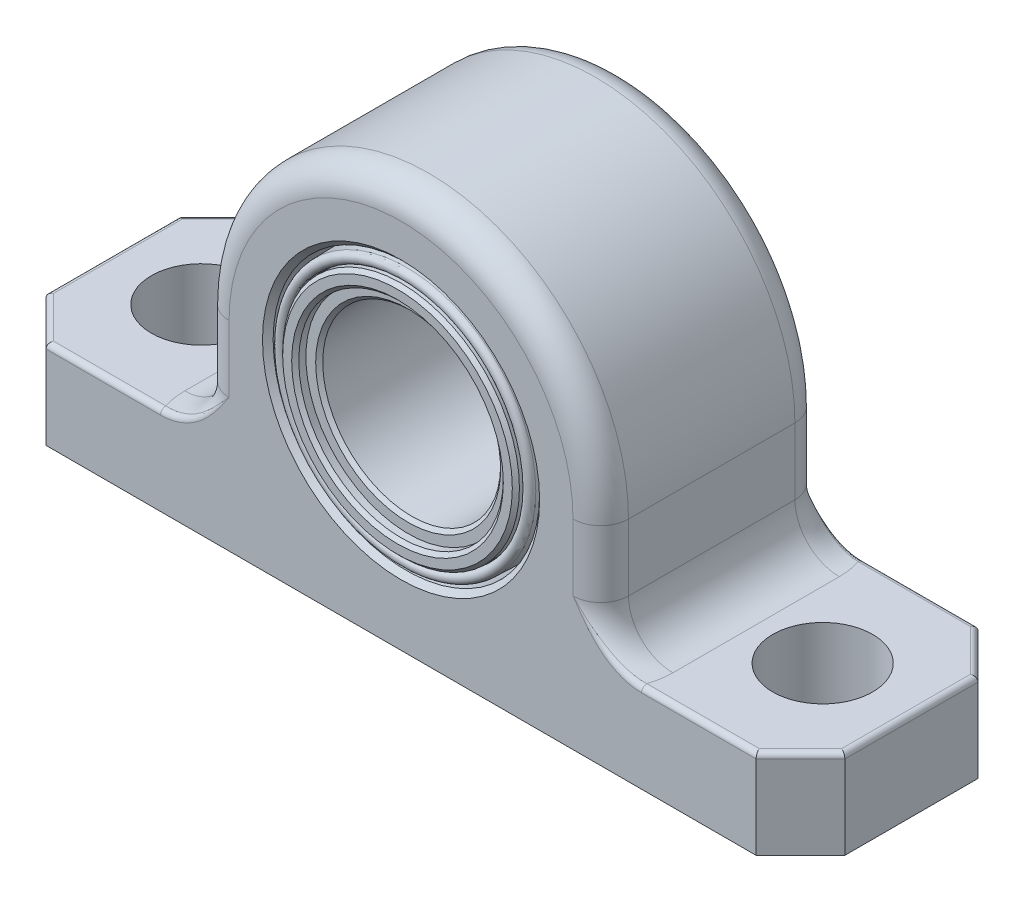
SolidWorks part; units mm, degrees
ref_plane "Front Plane" through (0, 0, 0) normal (0, 0, 1) x (1, 0, 0)
ref_plane "Top Plane" through (0, 0, 0) normal (0, 1, 0) x (1, 0, 0)
ref_plane "Right Plane" through (0, 0, 0) normal (1, 0, 0) x (0, 0, -1)
sketch "Sketch1" plane through (0, 0, 0) normal (0, 0, 1) x (1, 0, 0)
  line L0 (-28.575, 0) -> (28.575, 0)
  line L1 (28.575, 0) -> (28.575, 6.35)
  line L2 (-28.575, 0) -> (-28.575, 6.35)
  line L3 (-28.575, 6.35) -> (-14.2875, 6.35)
  line L4 (28.575, 6.35) -> (14.2875, 6.35)
  line L5 (-14.2875, 6.35) -> (-14.2875, 14.2875)
  line L6 (14.2875, 6.35) -> (14.2875, 14.2875)
  line L7 (0, 0) -> (0, 28.575) construction
  line L8 (4.4991, 18.7866) -> (10.1028, 24.3903) construction
  circle A0 centre (0, 14.2875) radius 6.3627
  arc A1 (14.2875, 14.2875) -> (-14.2875, 14.2875) centre (0, 14.2875) ccw
  circle A2 centre (0, 14.2875) radius 9.5326 construction
  point P16 (6.7406, 21.0281)
  point P17 (0, 20.6502)
  point P18 (0, 23.8201)
  dimension "D1" = 45
  dimension "ID" = 12.7254
  dimension "Overall Height" = 28.575
  dimension "Overall Length" = 57.15
  dimension "CAD B" = 6.35
  dimension "Center Height" = 14.2875
  dimension "D2" = 7.9248
  dimension "D3" = 3.1699
sketch "Sketch2" plane through (0, 0, 0) normal (0, 1, 0) x (1, 0, 0)
  line L0 (-22.225, 0) -> (22.225, 0) construction
  line L1 (-28.575, -7.9375) -> (28.575, 7.9375) construction
  line L2 (-28.575, 7.9375) -> (28.575, 7.9375)
  line L3 (-28.575, 7.9375) -> (-28.575, -7.9375)
  line L4 (-28.575, -7.9375) -> (28.575, -7.9375)
  line L5 (28.575, 7.9375) -> (28.575, -7.9375)
  circle A0 centre (-22.225, 0) radius 3.5719
  circle A1 centre (22.225, 0) radius 3.5719
  dimension "Mounting Hole" = 7.1437
  dimension "Mounting Center" = 44.45
  dimension "Overall Width" = 15.875
sketch "Sketch3" plane through (0, 0, 0) normal (0, 0, 1) x (1, 0, 0)
  line L0 (-28.575, 0) -> (-28.575, 6.35) construction
  line L1 (-28.575, 0) -> (28.575, 0) construction
  line L2 (-28.575, 6.35) -> (-14.2875, 6.35) construction
  line L3 (28.575, 6.35) -> (14.2875, 6.35) construction
  line L4 (28.575, 0) -> (28.575, 6.35) construction
  line L5 (14.2875, 6.35) -> (14.2875, 14.2875) construction
  line L6 (-14.2875, 6.35) -> (-14.2875, 14.2875) construction
  line L7 (-28.575, 0) -> (-28.575, 6.35)
  line L8 (-28.575, 0) -> (28.575, 0)
  line L9 (-28.575, 6.35) -> (-14.2875, 6.35)
  line L10 (28.575, 6.35) -> (14.2875, 6.35)
  line L11 (28.575, 0) -> (28.575, 6.35)
  line L12 (14.2875, 6.35) -> (14.2875, 14.2875)
  line L13 (-14.2875, 6.35) -> (-14.2875, 14.2875)
  arc A0 (14.2875, 14.2875) -> (-14.2875, 14.2875) centre (0, 14.2875) ccw construction
  circle A1 centre (0, 14.2875) radius 9.5326 construction
  arc A2 (14.2875, 14.2875) -> (-14.2875, 14.2875) centre (0, 14.2875) ccw
  circle A3 centre (0, 14.2875) radius 9.5326
extrude "Boss-Extrude1" add sketch "Sketch3" against normal up to vertex (7.9375 mm away) and the other way up to vertex (7.9375 mm away) up to point (-28.575, 0, -7.9375) other way up to point (-28.575, 0, 7.9375)
sketch "Sketch4" plane through (0, 0, 0) normal (0, 1, 0) x (1, 0, 0)
  circle A0 centre (-22.225, 0) radius 3.5719 construction
  circle A1 centre (22.225, 0) radius 3.5719 construction
  circle A2 centre (-22.225, 0) radius 3.5719
  circle A3 centre (22.225, 0) radius 3.5719
extrude "Cut-Extrude1" cut sketch "Sketch4" along normal through all
chamfer "Chamfer1" distance 3.175 angle 45 4 edges at (-28.575, 3.175, -7.9375) (28.575, 3.175, 7.9375) (28.575, 3.175, -7.9375) (-28.575, 3.175, 7.9375)
fillet "Fillet1" radius 1.9844 6 edges at (-14.2875, 10.3188, -7.9375) (0, 28.575, -7.9375) (-14.2875, 10.3188, 7.9375) (0, 28.575, 7.9375) (14.2875, 10.3187, -7.9375) (14.2875, 10.3187, 7.9375)
fillet "Fillet2" radius 3.175 6 edges at (-13.7063, 6.35, -7.3563) (-13.7063, 6.35, 7.3563) (13.7063, 6.35, -7.3563) (13.7063, 6.35, 7.3563) (-14.2875, 6.35, 0) (14.2875, 6.35, 0)
chamfer "Chamfer2" distance 0.381 angle 45 2 edges at (9.5326, 14.2875, 7.9375) (9.5326, 14.2875, -7.9375)
fillet "Fillet3" radius 0.381 14 edges at (-15.7758, 6.5694, -7.9375) (-15.7758, 6.5694, 7.9375) (15.7758, 6.5694, -7.9375) (15.7758, 6.5694, 7.9375) (-21.2328, 6.35, -7.9375) (-26.9875, 6.35, -6.35) (-28.575, 6.35, 0) (-26.9875, 6.35, 6.35) (-21.2328, 6.35, 7.9375) (21.2328, 6.35, -7.9375) (26.9875, 6.35, -6.35) (28.575, 6.35, 0) (26.9875, 6.35, 6.35) (21.2328, 6.35, 7.9375)
sketch "Sketch5" plane through (0, 0, 0) normal (1, 0, 0) x (0, 0, -1)
  line L1 (-7.9375, 23.8201) -> (7.9375, 23.8201)
  line L2 (-7.9375, 23.8201) -> (-7.9375, 20.6502)
  line L3 (-7.9375, 20.6502) -> (7.9375, 20.6502)
  line L4 (7.9375, 23.8201) -> (7.9375, 20.6502)
sketch "Sketch6" plane through (0, 0, 0) normal (1, 0, 0) x (0, 0, -1)
  line L0 (0, 23.8201) -> (7.9375, 23.8201)
  line L1 (-7.9375, 23.8201) -> (7.9375, 23.8201) construction
  line L2 (0, 23.8201) -> (-7.5661, 23.5559)
  line L3 (-7.9375, 23.8201) -> (-7.9375, 20.6502) construction
  line L4 (-7.4295, 22.8067) -> (-7.4295, 22.7573)
  line L5 (-7.4295, 22.7573) -> (-8.1915, 22.7573)
  line L6 (-8.1915, 22.7573) -> (-8.1915, 21.6046)
  line L7 (-8.1915, 21.6046) -> (-7.4295, 21.6046)
  line L8 (-7.4295, 21.6046) -> (-7.4295, 20.6502)
  line L9 (-7.9375, 20.6502) -> (7.9375, 20.6502) construction
  line L10 (-7.4295, 20.6502) -> (7.1755, 20.6502)
  line L11 (7.9375, 23.8201) -> (7.9375, 22.8067)
  line L12 (7.9375, 23.8201) -> (7.9375, 20.6502) construction
  line L13 (7.9375, 22.8067) -> (5.3975, 22.8067)
  line L14 (5.3975, 22.8067) -> (5.3975, 22.7573)
  line L15 (5.3975, 22.7573) -> (7.9375, 22.7573)
  line L16 (7.9375, 22.7573) -> (7.9375, 21.6046)
  line L17 (7.9375, 21.6046) -> (7.1755, 21.6046)
  line L18 (7.1755, 21.6046) -> (7.1755, 20.6502)
  line L19 (-7.9375, 26.5906) -> (-7.9375, 14.2875) construction
  line L20 (-7.9375, 14.2875) -> (7.9375, 14.2875) construction
  line L21 (-7.9375, 0) -> (-7.9375, 5.969) construction
  line L22 (-4.7625, 0) -> (-7.9375, 0) construction
  line L23 (7.9375, 0) -> (4.7625, 0) construction
  arc A0 (-7.5661, 23.5559) -> (-7.4295, 22.8067) centre (-7.5526, 23.1713) ccw
  point P33 (7.9375, 0)
  point P34 (-7.9375, 0)
  dimension "D2" = 0.254
  dimension "D1" = 2
  dimension "D3" = 0.762
  dimension "D4" = 3.1699
  dimension "D6" = 2.54
  dimension "D7" = 1.1527
  dimension "D8" = 0.7493
  dimension "D9" = 14.6342
  dimension "Bearing Width" = 15.875
revolve "Revolve1" add sketch "Sketch6" angle 360 about L20
chamfer "Chamfer3" distance 0.254 angle 45 6 edges at (7.3171, 14.2875, -7.9375) (8.4698, 14.2875, -7.9375) (6.3627, 14.2875, 7.4295) (6.3627, 14.2875, -7.1755) (8.4698, 14.2875, 8.1915) (7.3171, 14.2875, 8.1915)
ref_plane "Contact Plane 1" through (0, 28.575, 0) normal (0, 1, 0) x (1, 0, 0)
ref_plane "Contact Plane 2" through (0, 0, 0) normal (0, 1, 0) x (1, 0, 0)
ref_plane "Contact Plane 3" through (28.575, 0, 0) normal (1, 0, 0) x (0, 0, -1)
ref_plane "Contact Plane 4" through (-28.575, 0, 0) normal (1, 0, 0) x (0, 0, -1)
ref_axis "Center Axis 1" through (0, 14.2875, -7.5565) along (0, 0, 1)
equation "\"D3@Sketch1\"=\"D2@Sketch1\"/2.50"
equation "\"D1@Fillet1\"=\"Overall Width@Sketch2\"/8"
equation "\"D7@Sketch6\"=\"D4@Sketch6\"/2.750"
equation "\"D8@Sketch6\"=\"D7@Sketch6\"*.65"
equation "\"D9@Sketch6\"=\"ID@Sketch1\"*1.15"
equation "\"D1@Chamfer1\"=\"Overall Width@Sketch2\"/5"
